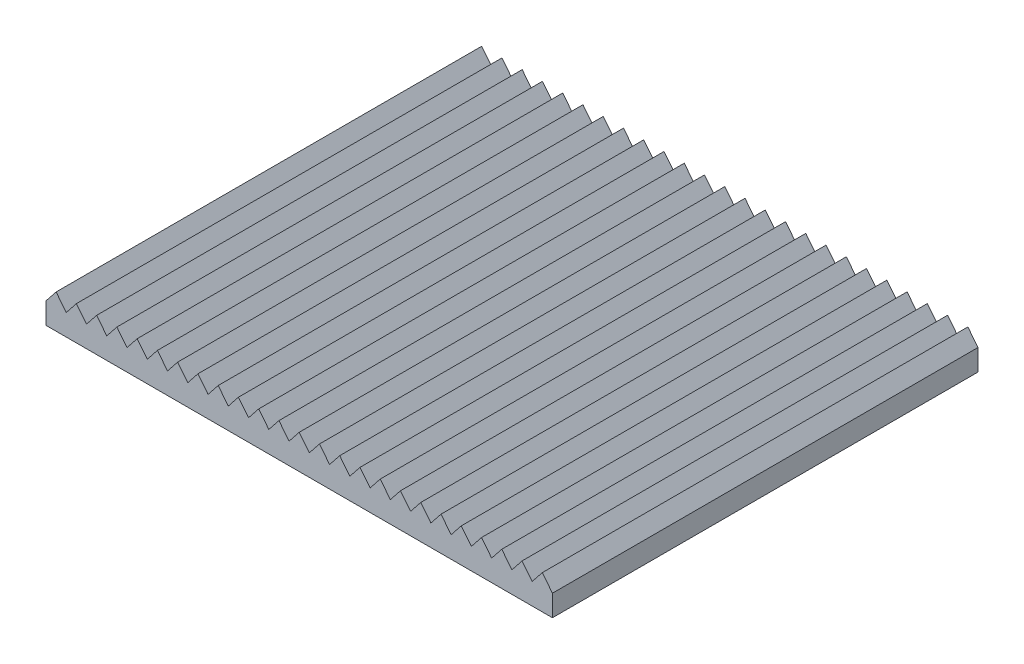
SolidWorks part; units mm, degrees
ref_plane "Front Plane" through (0, 0, 0) normal (0, 0, 1) x (1, 0, 0)
ref_plane "Top Plane" through (0, 0, 0) normal (0, 1, 0) x (1, 0, 0)
ref_plane "Right Plane" through (0, 0, 0) normal (1, 0, 0) x (0, 0, -1)
sketch "Sketch1" plane through (0, 0, 0) normal (0, 1, 0) x (1, 0, 0)
  line L6 (-29.75, 25) -> (29.75, 25)
  line L28 (-29.75, 25) -> (-29.75, -25)
  line L29 (-29.75, -25) -> (29.75, -25)
  line L30 (29.75, 25) -> (29.75, -25)
  line L31 (-29.75, 25) -> (29.75, -25) construction
  line L32 (-29.75, -25) -> (29.75, 25) construction
  circle A1 centre (0, 0) radius 3
  point P0 (0, 0)
  dimension "D3" = 6
  dimension "D1" = 59.5
  dimension "D2" = 50
extrude "Boss-Extrude1" add sketch "Sketch1" along normal blind 1.5
sketch "Sketch2" plane through (0, 0, -25) normal (0, 0, -1) x (-1, 0, 0)
  line L0 (-29.75, 1.5) -> (-29.75, 0) construction
  line L1 (-29.75, 1.5) -> (29.75, 1.5)
  line L2 (-29.75, 1.5) -> (-29.75, 2.5)
  line L4 (29.75, 1.5) -> (29.75, 2.5)
  line L5 (-1.19, 2.5) -> (0, 4)
  line L6 (0, 0.825) -> (0, -0.825) construction
  line L7 (1.19, 2.5) -> (0, 4)
  line L8 (1.19, 2.5) -> (2.38, 4)
  line L9 (3.57, 2.5) -> (2.38, 4)
  line L10 (3.57, 2.5) -> (4.76, 4)
  line L11 (5.95, 2.5) -> (4.76, 4)
  line L12 (5.95, 2.5) -> (7.14, 4)
  line L13 (8.33, 2.5) -> (7.14, 4)
  line L14 (8.33, 2.5) -> (9.52, 4)
  line L15 (10.71, 2.5) -> (9.52, 4)
  line L16 (10.71, 2.5) -> (11.9, 4)
  line L17 (13.09, 2.5) -> (11.9, 4)
  line L18 (13.09, 2.5) -> (14.28, 4)
  line L19 (15.47, 2.5) -> (14.28, 4)
  line L20 (15.47, 2.5) -> (16.66, 4)
  line L21 (17.85, 2.5) -> (16.66, 4)
  line L22 (17.85, 2.5) -> (19.04, 4)
  line L23 (20.23, 2.5) -> (19.04, 4)
  line L24 (20.23, 2.5) -> (21.42, 4)
  line L25 (22.61, 2.5) -> (21.42, 4)
  line L26 (22.61, 2.5) -> (23.8, 4)
  line L27 (24.99, 2.5) -> (23.8, 4)
  line L28 (24.99, 2.5) -> (26.18, 4)
  line L29 (27.37, 2.5) -> (26.18, 4)
  line L30 (27.37, 2.5) -> (28.56, 4)
  line L31 (29.75, 2.5) -> (28.56, 4)
  line L32 (-29.75, 2.5) -> (-28.56, 4)
  line L33 (-27.37, 2.5) -> (-28.56, 4)
  line L34 (-27.37, 2.5) -> (-26.18, 4)
  line L35 (-24.99, 2.5) -> (-26.18, 4)
  line L36 (-24.99, 2.5) -> (-23.8, 4)
  line L37 (-22.61, 2.5) -> (-23.8, 4)
  line L38 (-22.61, 2.5) -> (-21.42, 4)
  line L39 (-20.23, 2.5) -> (-21.42, 4)
  line L40 (-20.23, 2.5) -> (-19.04, 4)
  line L41 (-17.85, 2.5) -> (-19.04, 4)
  line L42 (-17.85, 2.5) -> (-16.66, 4)
  line L43 (-15.47, 2.5) -> (-16.66, 4)
  line L44 (-15.47, 2.5) -> (-14.28, 4)
  line L45 (-13.09, 2.5) -> (-14.28, 4)
  line L46 (-13.09, 2.5) -> (-11.9, 4)
  line L47 (-10.71, 2.5) -> (-11.9, 4)
  line L48 (-10.71, 2.5) -> (-9.52, 4)
  line L49 (-8.33, 2.5) -> (-9.52, 4)
  line L50 (-8.33, 2.5) -> (-7.14, 4)
  line L51 (-5.95, 2.5) -> (-7.14, 4)
  line L52 (-5.95, 2.5) -> (-4.76, 4)
  line L53 (-3.57, 2.5) -> (-4.76, 4)
  line L54 (-3.57, 2.5) -> (-2.38, 4)
  line L55 (-1.19, 2.5) -> (-2.38, 4)
  point P49 (0, 0)
  dimension "D1" = 1
  dimension "D2" = 1.5
  dimension "D3" = 13
extrude "Boss-Extrude2" add sketch "Sketch2" against normal blind 50
sketch "Sketch3" plane through (0, 0, 0) normal (0, -1, 0) x (-1, 0, 0)
  line L0 (0, 2.2) -> (0, -2.2) construction
  line L2 (-1.75, -2.4367) -> (-1.75, -5)
  line L3 (-1.75, -5) -> (1.75, -5)
  line L4 (1.75, -2.4367) -> (1.75, -5)
  arc A0 (1.75, -2.4367) -> (-1.75, -2.4367) centre (0, 0) ccw
  point P7 (0, 0)
  dimension "D2" = 6
  dimension "D1" = 3.5
  dimension "D3" = 5
  dimension "D4" = 1.75
extrude "Cut-Extrude1" cut sketch "Sketch3" against normal blind 2
chamfer "Chamfer1" distance 2 angle 45 1 edges at (0, 0, 5)
